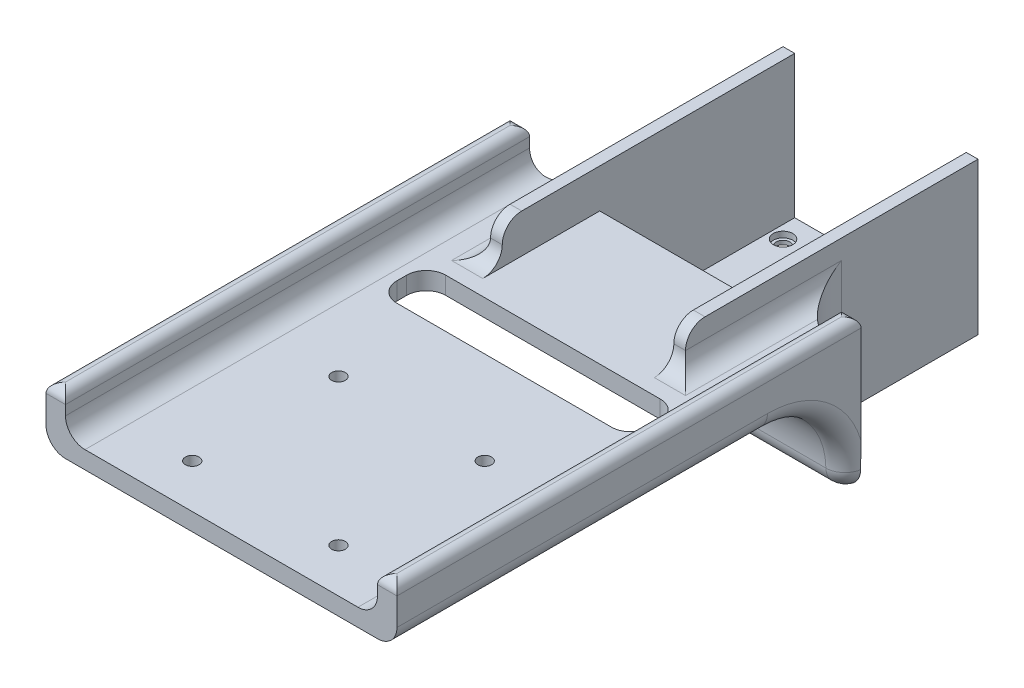
SolidWorks part; units mm, degrees
ref_plane "Front Plane" through (0, 0, 0) normal (0, 0, 1) x (1, 0, 0)
ref_plane "Top Plane" through (0, 0, 0) normal (0, 1, 0) x (1, 0, 0)
ref_plane "Right Plane" through (0, 0, 0) normal (1, 0, 0) x (0, 0, -1)
sketch "Sketch1" plane through (0, 0, 0) normal (0, 1, 0) x (1, 0, 0)
  line L0 (0, 44.3291) -> (0, -49.0863) construction
  line L1 (-50, 50) -> (50, 50)
  line L2 (-50, 50) -> (-50, -50)
  line L3 (-50, -50) -> (50, -50)
  line L4 (50, 50) -> (50, -50)
  line L5 (-50, 50) -> (50, -50) construction
  line L6 (-50, -50) -> (50, 50) construction
  line L7 (-55.6456, 0) -> (53.7715, 0) construction
  circle A0 centre (-37.5, 37.5) radius 3.5
  circle A1 centre (37.5, 37.5) radius 3.5
  circle A2 centre (37.5, -37.5) radius 3.5
  circle A3 centre (-37.5, -37.5) radius 3.5
  point P1 (0, 0)
  dimension "D1" = 75
  dimension "D2" = 75
  dimension "D4" = 7
  dimension "D3" = 100
extrude "Boss-Extrude1" add sketch "Sketch1" along normal blind 5
sketch "Sketch6" plane through (0, 0, 0) normal (0, -1, 0) x (1, 0, 0)
  line L0 (59.8047, 0) -> (-72.4197, 0) construction
  line L1 (0, 49.555) -> (0, -51.1902) construction
  circle A0 centre (-37.5, 37.5) radius 5
  circle A1 centre (37.5, 37.5) radius 5
  circle A2 centre (37.5, -37.5) radius 5
  circle A3 centre (-37.5, -37.5) radius 5
  dimension "D1" = 10
extrude "Cut-Extrude1" cut sketch "Sketch6" along normal blind 3 from surface starting at face at (37.5, 5, 41)
sketch "Sketch8" plane through (-50, 0, 0) normal (-1, 0, 0) x (0, 0, 1)
  line L1 (50, 0) -> (58, 0)
  line L2 (50, 0) -> (50, 58)
  line L3 (50, 58) -> (58, 58)
  line L4 (58, 0) -> (58, 58)
  dimension "D1" = 8
  dimension "D2" = 58
extrude "Boss-Extrude2" add sketch "Sketch8" against normal blind 180 from offset 40
sketch "Sketch9" plane through (0, 0, 58) normal (0, 0, 1) x (1, 0, 0)
  line L7 (90, 0) -> (90, 58) construction
  line L8 (-90, 58) -> (90, 58)
  line L9 (-90, 58) -> (-90, 49)
  line L10 (-90, 49) -> (90, 49)
  line L11 (90, 58) -> (90, 49)
  dimension "D1" = 9
extrude "Boss-Extrude3" add sketch "Sketch9" along normal blind 230
sketch "Sketch13" plane through (0, 58, 0) normal (0, 1, 0) x (1, 0, 0)
  line L0 (90, -288) -> (-90, -288) construction
  line L5 (-37.5, -190.5) -> (37.5, -265.5) construction
  line L6 (-37.5, -265.5) -> (37.5, -190.5) construction
  line L7 (0, -276.3326) -> (0, -189.7195) construction
  line L12 (-28.4717, -228) -> (37, -228) construction
  circle A1 centre (-37.5, -190.5) radius 3.5
  circle A2 centre (37.5, -190.5) radius 3.5
  circle A3 centre (37.5, -265.5) radius 3.5
  circle A4 centre (-37.5, -265.5) radius 3.5
  point P0 (0, -228)
  dimension "D2" = 7
  dimension "D1" = 75
  dimension "D3" = 75
  dimension "D4" = 60
extrude "Cut-Extrude3" cut sketch "Sketch13" along direction (0, 1, 0) on the side against the normal up to next (9 mm away)
sketch "Sketch15" plane through (0, 5, 0) normal (0, 1, 0) x (1, 0, 0)
  line L0 (-50, -50) -> (50, -50) construction
  line L1 (-50, 50) -> (-44, 50)
  line L2 (-50, 50) -> (-50, -50)
  line L3 (-50, -50) -> (-44, -50)
  line L4 (-44, 50) -> (-44, -50)
  line L6 (50, 50) -> (44, 50)
  line L7 (50, 50) -> (50, -50)
  line L8 (50, -50) -> (44, -50)
  line L9 (44, 50) -> (44, -50)
  dimension "D1" = 6
extrude "Boss-Extrude6" add sketch "Sketch15" along normal offset from surface (73 mm away) 20 up to face at (-37.5, 58, 262) offset beyond the face yes
sketch "Sketch16" plane through (0, 58, 0) normal (0, 1, 0) x (1, 0, 0)
  line L0 (0, -85.9399) -> (0, -175.0601) construction
  line L1 (-50, -50) -> (-90, -50) construction
  line L2 (-65, -118) -> (65, -118)
  line L3 (-65, -118) -> (-65, -143)
  line L4 (-65, -143) -> (65, -143)
  line L5 (65, -118) -> (65, -143)
  line L6 (-65, -118) -> (65, -143) construction
  line L7 (-65, -143) -> (65, -118) construction
  point P3 (0, -130.5)
  dimension "D1" = 68
  dimension "D2" = 25
  dimension "D3" = 130
extrude "Cut-Extrude4" cut sketch "Sketch16" against normal up to next
fillet "Fillet1" radius 40 1 edges at (0, 49, 58)
fillet "Fillet2" radius 10 4 edges at (-65, 53.5, 143) (65, 53.5, 143) (65, 53.5, 118) (-65, 53.5, 118)
sketch "Sketch17" plane through (0, 0, 50) normal (0, 0, 1) x (1, 0, 0)
  line L4 (90, 58) -> (-90, 58) construction
  line L5 (-44, 78) -> (-50, 78)
  line L6 (-44, 78) -> (-44, 58)
  line L7 (-44, 58) -> (-50, 58)
  line L8 (-50, 78) -> (-50, 58)
  line L9 (50, 78) -> (44, 78)
  line L10 (50, 78) -> (50, 58)
  line L11 (50, 58) -> (44, 58)
  line L12 (44, 78) -> (44, 58)
  line L13 (50, 58) -> (44, 58) construction
  dimension "D1" = 6
extrude "Boss-Extrude7" add sketch "Sketch17" along normal blind 50
fillet "Fillet3" radius 10 2 edges at (47, 78, 100) (-47, 78, 100)
fillet "Fillet4" radius 10 2 edges at (47, 58, 100) (-47, 58, 100)
fillet "Fillet6" radius 30 2 edges at (50, 29, 50) (-50, 29, 50)
fillet "Fillet7" radius 10 1 edges at (0, 0, 58)
sketch "Sketch18" plane through (0, 58, 0) normal (0, 1, 0) x (1, 0, 0)
  line L0 (90, -288) -> (-90, -288) construction
  line L1 (-90, -50) -> (-80, -50)
  line L2 (-90, -50) -> (-90, -288)
  line L3 (-90, -288) -> (-80, -288)
  line L4 (-80, -50) -> (-80, -288)
  line L6 (90, -50) -> (80, -50)
  line L7 (90, -50) -> (90, -288)
  line L8 (90, -288) -> (80, -288)
  line L9 (80, -50) -> (80, -288)
  dimension "D1" = 10
extrude "Boss-Extrude8" add sketch "Sketch18" along normal blind 20
fillet "Fillet8" radius 10 8 edges at (90, 49, 193) (90, 3.5944, 55.6891) (-90, 3.5944, 55.6891) (-90, 49, 193) (80, 58, 169) (-80, 58, 169) (90, 37.5657, 70) (-90, 37.5657, 70)
fillet "Fillet9" radius 10 2 edges at (50, 58, 65) (-50, 58, 65)
fillet "Fillet10" radius 5 8 edges at (-85, 78, 50) (-80, 78, 169) (-85, 78, 288) (-90, 78, 169) (85, 78, 288) (80, 78, 169) (85, 78, 50) (90, 78, 169)
